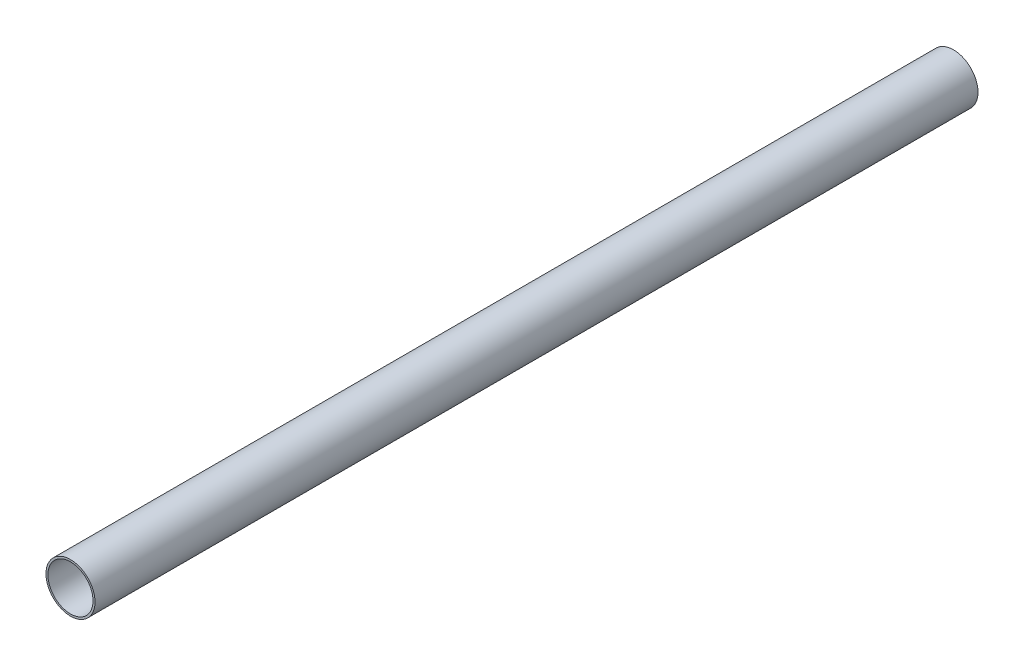
SolidWorks part; units mm, degrees
ref_plane "Спереди" through (0, 0, 0) normal (0, 0, 1) x (1, 0, 0)
ref_plane "Сверху" through (0, 0, 0) normal (0, 1, 0) x (1, 0, 0)
ref_plane "Справа" through (0, 0, 0) normal (1, 0, 0) x (0, 0, -1)
other "Configuration Table"
sketch "Эскиз1" plane through (0, 0, 0) normal (0, 0, 1) x (1, 0, 0)
  circle A0 centre (0, 0) radius 50
  circle A1 centre (0, 0) radius 46
  dimension "D1" = 100
  dimension "D2" = 4
extrude "Бобышка-Вытянуть1" add sketch "Эскиз1" along normal blind 1800
ref_axis "Ось1" through (0, 0, 1800) along (0, 0, -1)
